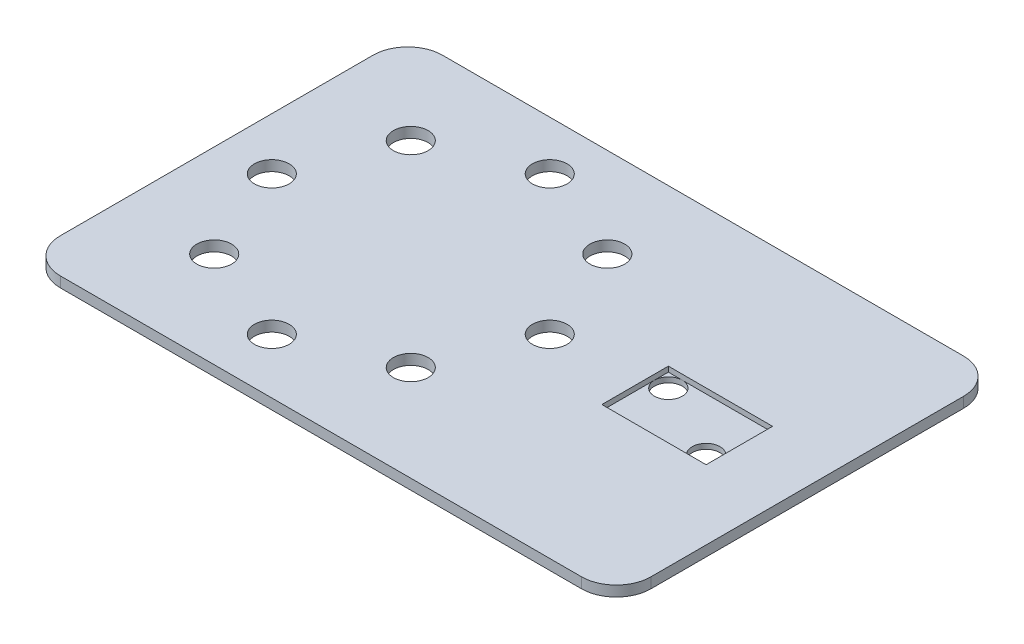
SolidWorks part; units mm, degrees
ref_plane "Front Plane" through (0, 0, 0) normal (0, 0, 1) x (1, 0, 0)
ref_plane "Top Plane" through (0, 0, 0) normal (0, 1, 0) x (1, 0, 0)
ref_plane "Right Plane" through (0, 0, 0) normal (1, 0, 0) x (0, 0, -1)
sketch "Sketch1" plane through (0, 0, 0) normal (0, 1, 0) x (1, 0, 0)
  line L0 (-37.5, 0) -> (-15, 0) construction
  line L6 (42.5, -27.9333) -> (-42.5, -27.9333)
  line L7 (32.5, -5) -> (17.5, -5)
  line L8 (32.5, -5) -> (32.5, 4.5667)
  line L9 (32.5, 4.5667) -> (17.5, 4.5667)
  line L10 (17.5, -5) -> (17.5, 4.5667)
  line L11 (32.5, -5) -> (17.5, 4.5667) construction
  line L12 (32.5, 4.5667) -> (17.5, -5) construction
  line L13 (42.5, -27.9333) -> (42.5, 27.0667)
  line L14 (42.5, 27.0667) -> (-42.5, 27.0667)
  line L15 (-42.5, -27.9333) -> (-42.5, 27.0667)
  circle A0 centre (-35, 0) radius 2.5
  circle A2 centre (-29.1421, 14.1421) radius 2.5
  circle A3 centre (-15, 20) radius 2.5
  circle A4 centre (-0.8579, 14.1421) radius 2.5
  circle A5 centre (5, 0) radius 2.5
  circle A6 centre (-0.8579, -14.1421) radius 2.5
  circle A7 centre (-15, -20) radius 2.5
  circle A8 centre (-29.1421, -14.1421) radius 2.5
  point P0 (0, 0)
  point P6 (25, -0.2166)
  dimension "D3" = 5
  dimension "D4" = 10
  dimension "D1" = 55
  dimension "D2" = 85
  dimension "D5" = 22.5
  dimension "D6" = 22.5
  dimension "D9" = 15
  dimension "D7" = 8
extrude "Boss-Extrude3" add sketch "Sketch1" along normal blind 1.5
fillet "Fillet2" radius 5 4 edges at (42.5, 0.75, -27.0667) (-42.5, 0.75, -27.0667) (-42.5, 0.75, 27.9333) (42.5, 0.75, 27.9333)
sketch "Sketch2" plane through (17.5, 0, 0) normal (1, 0, 0) x (0, 0, -1)
  line L0 (-5, 1.5) -> (-5, 0) construction
  line L1 (4.5667, 0) -> (-5, 0)
  line L2 (4.5667, 0) -> (4.5667, 0.75)
  line L3 (4.5667, 0.75) -> (-5, 0.75)
  line L4 (-5, 0) -> (-5, 0.75)
  dimension "D1" = 0.75
extrude "Boss-Extrude4" add sketch "Sketch2" along normal up to next
sketch "Sketch3" plane through (0, 0.75, 0) normal (0, 1, 0) x (1, 0, 0)
  line L0 (32.5, -5) -> (32.5, 4.5667) construction
  line L6 (17.5, -5) -> (32.5, -5) construction
  line L7 (32.5, 4.5667) -> (17.5, 4.5667) construction
  line L8 (17.5, 4.5667) -> (17.5, -5) construction
  circle A4 centre (19.5, 2.5667) radius 2
  circle A5 centre (30.5, -3) radius 2
  point P8 (32.0312, -5)
  dimension "D1" = 4
  dimension "D2" = 4
  dimension "D3" = 2
  dimension "D4" = 2
  dimension "D5" = 2
  dimension "D6" = 2
extrude "Cut-Extrude1" cut sketch "Sketch3" against normal blind 10 contours A5 | A4 region at (30.5, 0.75, 3)
